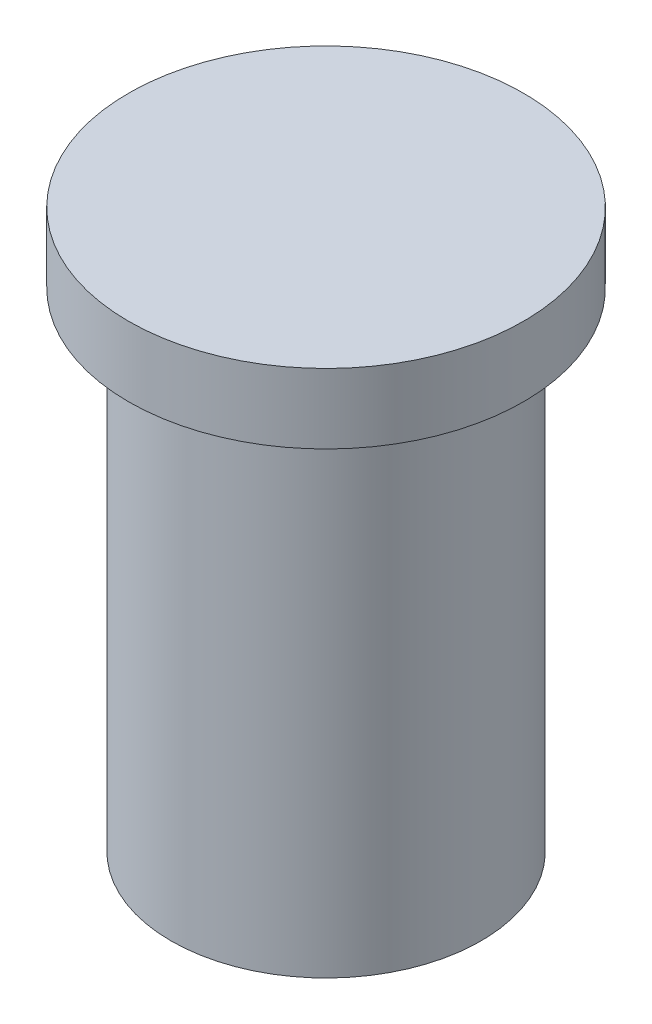
SolidWorks part; units mm, degrees
ref_plane "Front Plane" through (0, 0, 0) normal (0, 0, 1) x (1, 0, 0)
ref_plane "Top Plane" through (0, 0, 0) normal (0, 1, 0) x (1, 0, 0)
ref_plane "Right Plane" through (0, 0, 0) normal (1, 0, 0) x (0, 0, -1)
sketch "Sketch1" plane through (0, 0, 0) normal (0, 1, 0) x (1, 0, 0)
  circle A0 centre (0, 0) radius 28.321
  circle A1 centre (0, 0) radius 22.225
  dimension "D1" = 56.642
  dimension "D2" = 44.45
extrude "Boss-Extrude1" add sketch "Sketch1" along normal blind 10
extrude "Boss-Extrude2" add sketch "Sketch1<2>" against normal blind 70 separate body contours A1 region at (0, 0, 0)
sketch "Sketch1<2>" plane through (0, 0, 0) normal (0, 1, 0) x (1, 0, 0) same geometry as "Sketch1"
extrude "Boss-Extrude3" add sketch "Sketch1<3>" along normal up to surface (10 mm away) contours A1 region at (0, 0, 0) up to face at (0, 10, 28.321)
sketch "Sketch1<3>" plane through (0, 0, 0) normal (0, 1, 0) x (1, 0, 0) same geometry as "Sketch1"
